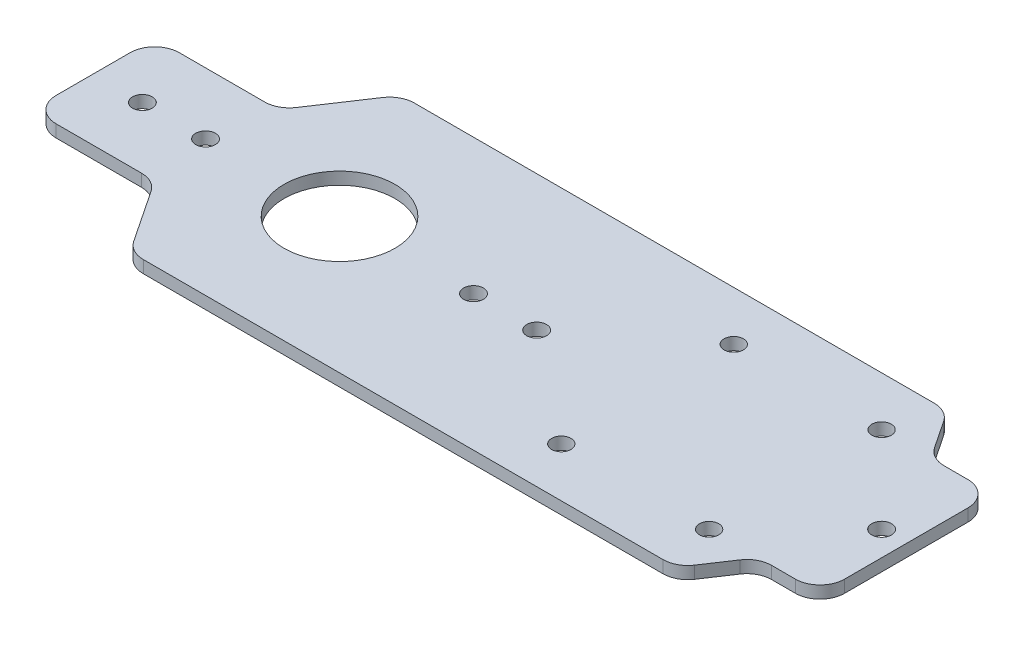
SolidWorks part; units mm, degrees
material "6061 Alloy"
ref_plane "Front Plane" through (0, 0, 0) normal (0, 0, 1) x (1, 0, 0)
ref_plane "Top Plane" through (0, 0, 0) normal (0, 1, 0) x (1, 0, 0)
ref_plane "Right Plane" through (0, 0, 0) normal (1, 0, 0) x (0, 0, -1)
sketch "Sketch1" plane through (0, 0, 0) normal (0, 1, 0) x (1, 0, 0)
  line L0 (16.2686, 0) -> (85.3314, 0) construction
  line L1 (50.8, 0) -> (50.8, 3.1391) construction
  line L2 (19.05, 15.875) -> (31.75, 34.925)
  line L3 (-12.7, 15.875) -> (19.05, 15.875)
  line L4 (-12.7, 15.875) -> (-12.7, -15.875)
  line L5 (-12.7, -15.875) -> (19.05, -15.875)
  line L6 (114.3, 15.875) -> (114.3, -15.875)
  line L7 (-12.7, 15.875) -> (114.3, -15.875) construction
  line L8 (-12.7, -15.875) -> (114.3, 15.875) construction
  line L9 (31.75, 34.925) -> (69.85, 34.925)
  line L10 (69.85, 34.925) -> (82.55, 15.875)
  line L11 (50.8, 34.925) -> (50.8, 29.0511) construction
  line L12 (69.85, -34.925) -> (82.55, -15.875)
  line L13 (31.75, -34.925) -> (69.85, -34.925)
  line L14 (19.05, -15.875) -> (31.75, -34.925)
  line L15 (82.55, -15.875) -> (114.3, -15.875)
  line L16 (82.55, 15.875) -> (114.3, 15.875)
  circle A0 centre (0, 0) radius 2.54
  circle A1 centre (101.6, 0) radius 2.54
  circle A2 centre (16.2686, 0) radius 2.54 construction
  circle A3 centre (85.3314, 0) radius 2.54 construction
  dimension "D1" = 5.08
  dimension "D3" = 127
  dimension "D4" = 31.75
  dimension "D5" = 69.0628
  dimension "D2" = 101.6
  dimension "D6" = 19.05
  dimension "D7" = 31.75
  dimension "D8" = 38.1
extrude "Boss-Extrude1" add sketch "Sketch1" along normal blind 3.175
sketch "Sketch2" plane through (0, 3.175, 0) normal (0, 1, 0) x (1, 0, 0)
  circle A0 centre (50.8, 0) radius 14.2875
  circle A1 centre (0, 0) radius 2.54 construction
  dimension "D1" = 50.8
  dimension "D2" = 28.575
extrude "Cut-Extrude1" cut sketch "Sketch2" against normal blind 3.175
sketch "Sketch3" plane through (0, 3.175, 0) normal (0, 1, 0) x (1, 0, 0)
  line L0 (50.8, 0) -> (50.8, 14.2875) construction
  circle A2 centre (85.3314, 0) radius 2.54
  circle A3 centre (16.2686, 0) radius 2.54
  circle A5 centre (50.8, 0) radius 14.2875 construction
  circle A6 centre (50.8, 0) radius 14.2875 construction
  dimension "D2" = 5.08
  dimension "D3" = 5.08
  dimension "D4" = 69.0628
extrude "Cut-Extrude2" cut sketch "Sketch3" against normal through all
sketch "Sketch5" plane through (0, 0, 0) normal (0, -1, 0) x (1, 0, 0)
  line L5 (114.3, 15.875) -> (114.3, -15.875) construction
  line L10 (69.85, -34.925) -> (196.85, -34.925)
  line L11 (69.85, -34.925) -> (69.85, 34.925)
  line L12 (69.85, 34.925) -> (196.85, 34.925)
  line L13 (196.85, -34.925) -> (196.85, 34.925)
  line L14 (114.554, 17.272) -> (183.896, 17.272) construction
  line L15 (114.554, 17.272) -> (114.554, -17.272) construction
  line L16 (114.554, -17.272) -> (183.896, -17.272) construction
  line L17 (183.896, 17.272) -> (183.896, -17.272) construction
  line L18 (172.5083, 34.925) -> (180.975, 22.225)
  line L19 (172.5083, -34.925) -> (180.975, -22.225)
  line L20 (180.975, -22.225) -> (196.85, -22.225)
  line L21 (82.55, -15.875) -> (69.85, -34.925) construction
  line L22 (82.55, -15.875) -> (69.85, -34.925)
  line L23 (69.85, 34.925) -> (82.55, 15.875) construction
  line L24 (69.85, 34.925) -> (82.55, 15.875)
  line L25 (180.975, 22.225) -> (196.85, 22.225)
  circle A4 centre (101.6, 0) radius 2.54 construction
  circle A5 centre (85.3314, 0) radius 2.54 construction
  circle A6 centre (101.6, 0) radius 2.54
  circle A7 centre (85.3314, 0) radius 2.54
  circle A8 centre (130.175, 22.225) radius 2.4892
  circle A9 centre (168.275, 22.225) radius 2.4892
  circle A10 centre (130.175, -22.225) radius 2.4892
  circle A11 centre (168.275, -22.225) radius 2.4892
  circle A12 centre (190.5, 0) radius 2.54
  line M15 (69.85, -34.925) -> (82.55, -15.875)
  line M16 (82.55, -15.875) -> (114.3, -15.875)
  line M17 (114.3, -15.875) -> (114.3, 15.875)
  line M18 (114.3, 15.875) -> (82.55, 15.875)
  line M19 (82.55, 15.875) -> (69.85, 34.925)
  dimension "D2" = 4.9784
  dimension "D3" = 44.45
  dimension "D4" = 38.1
  dimension "D11" = 15.621
  dimension "D16" = 88.9
  dimension "D5" = 4.953
  dimension "D6" = 82.55
  dimension "D7" = 17.653
  dimension "D8" = 0.254
  dimension "D9" = 69.342
  dimension "D10" = 34.544
  dimension "D12" = 15.875
  dimension "D13" = 12.7
  dimension "D14" = 15.875
  dimension "D15" = 12.7
extrude "Boss-Extrude2" add sketch "Sketch5" against normal up to surface (3.175 mm away) contours L25 L18 L12 L10 L19 L20 L13 A11 A10 A9 A8 M19 M18 M17 M16 M15 region at (139.8524, 0, 0) up to face at (85.3314, 3.175, 2.54)
fillet "Fillet1" radius 6.35 12 edges at (19.05, 1.5875, -15.875) (31.75, 1.5875, -34.925) (31.75, 1.5875, 34.925) (19.05, 1.5875, 15.875) (-12.7, 1.5875, -15.875) (-12.7, 1.5875, 15.875) (172.5083, 1.5875, -34.925) (180.975, 1.5875, -22.225) (196.85, 1.5875, -22.225) (196.85, 1.5875, 22.225) (180.975, 1.5875, 22.225) (172.5083, 1.5875, 34.925)
sketch "Sketch4"
